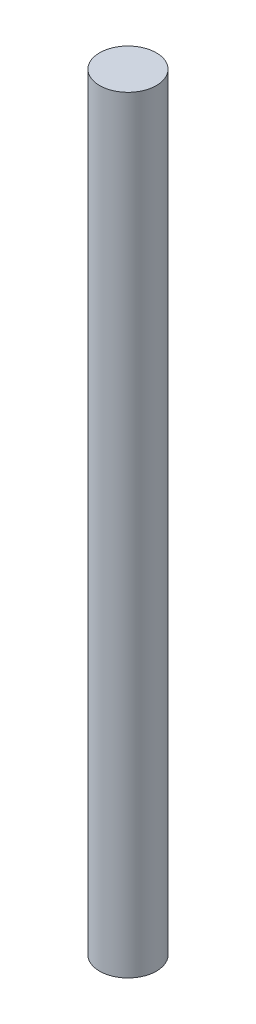
SolidWorks part; units mm, degrees
ref_plane "Front Plane" through (0, 0, 0) normal (0, 0, 1) x (1, 0, 0)
ref_plane "Top Plane" through (0, 0, 0) normal (0, 1, 0) x (1, 0, 0)
ref_plane "Right Plane" through (0, 0, 0) normal (1, 0, 0) x (0, 0, -1)
sketch "Sketch1" plane through (0, 0, 0) normal (0, 1, 0) x (1, 0, 0)
  circle A0 centre (0, 0) radius 1.4732
  dimension "D1" = 2.9464
extrude "Boss-Extrude1" add sketch "Sketch1" along normal blind 39.8272
